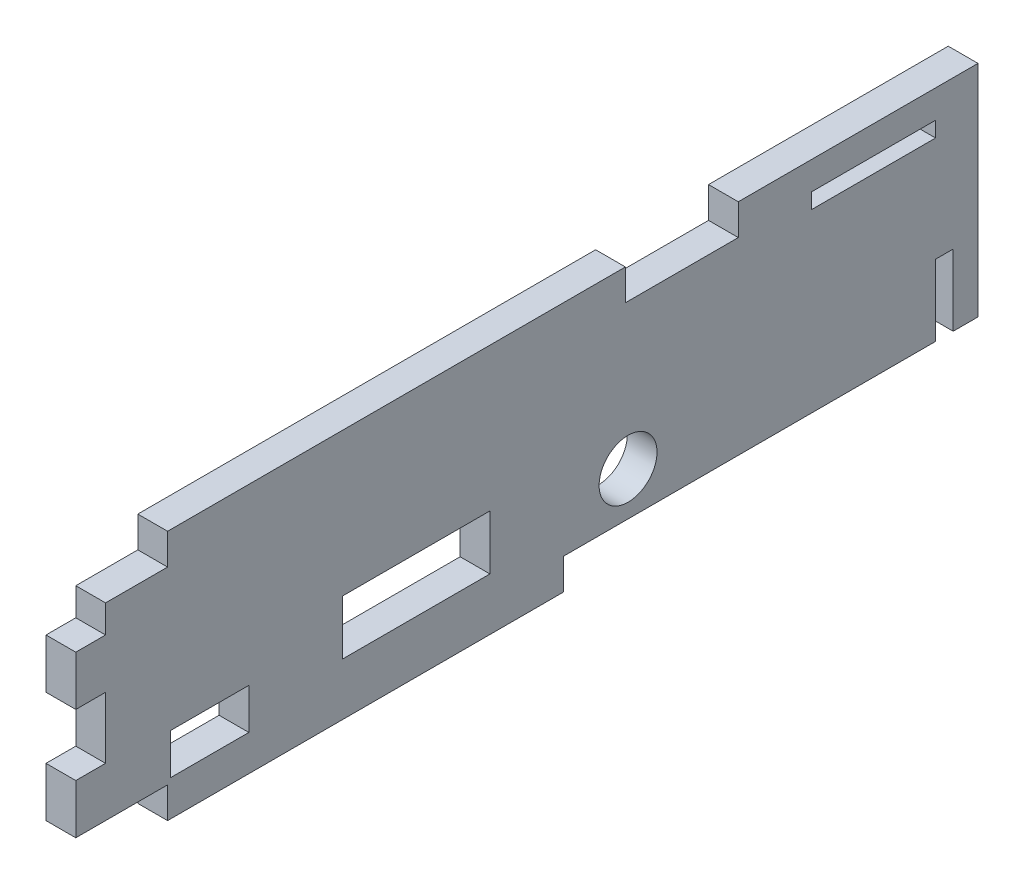
SolidWorks part; units mm, degrees
ref_plane "Front" through (0, 0, 0) normal (0, 0, 1) x (1, 0, 0)
ref_plane "Top" through (0, 0, 0) normal (0, 1, 0) x (1, 0, 0)
ref_plane "Right" through (0, 0, 0) normal (1, 0, 0) x (0, 0, -1)
sketch "Sketch2" plane through (0, 0, 0) normal (1, 0, 0) x (0, 0, -1)
  line L0 (0, 4.7244) -> (84.963, 4.7244) construction
  line L1 (0, 24.0284) -> (84.963, 24.0284)
  line L2 (0, 24.0284) -> (0, 0)
  line L3 (0, 0) -> (84.963, 0)
  line L4 (84.963, 24.0284) -> (84.963, 0)
  line L5 (6.6294, 9.3853) -> (14.6685, 9.3853)
  line L6 (6.6294, 9.3853) -> (6.6294, 5.207)
  line L7 (6.6294, 5.207) -> (14.6685, 5.207)
  line L8 (14.6685, 9.3853) -> (14.6685, 5.207)
  line L9 (24.257, 6.9215) -> (39.3446, 6.9215)
  line L10 (24.257, 6.9215) -> (24.257, 12.5095)
  line L11 (24.257, 12.5095) -> (39.3446, 12.5095)
  line L12 (39.3446, 6.9215) -> (39.3446, 12.5095)
  line L13 (53.486, 12.1412) -> (53.486, 4.7244) construction
  line L14 (6.35, 24.0284) -> (6.35, 27.2034)
  line L15 (6.35, 27.2034) -> (53.213, 27.2034)
  line L16 (84.963, 24.0284) -> (86.7664, 24.0284)
  line L17 (6.35, 4.7244) -> (6.35, 1.5494)
  line L18 (6.35, 1.5494) -> (46.863, 1.5494)
  line L19 (46.863, 1.5494) -> (46.863, 4.7244)
  line L20 (46.863, 4.7244) -> (84.963, 4.7244)
  line L21 (6.35, 4.7244) -> (0, 4.7244)
  line L22 (86.7664, 24.0284) -> (86.7664, 4.7244)
  line L23 (86.7664, 24.0284) -> (89.3064, 24.0284)
  line L24 (89.3064, 24.0284) -> (89.3064, 4.7244)
  line L25 (84.963, 12.0142) -> (86.7664, 12.0142)
  line L26 (86.7664, 4.7244) -> (89.3064, 4.7244)
  line L27 (84.963, 22.7584) -> (72.263, 22.7584)
  line L28 (42.4815, 24.0284) -> (42.4815, 0) construction
  line L29 (-3.048, 4.7244) -> (0, 4.7244)
  line L30 (-3.048, 9.8044) -> (-3.048, 4.7244)
  line L31 (-3.048, 9.8044) -> (0, 9.8044)
  line L32 (-3.048, 16.1036) -> (0, 16.1036)
  line L33 (-3.048, 21.1836) -> (-3.048, 16.1036)
  line L34 (0, 21.1836) -> (-3.048, 21.1836)
  line L35 (53.213, 27.2034) -> (53.213, 24.0284)
  line L36 (72.263, 22.7584) -> (72.263, 24.5618)
  line L37 (72.263, 24.5618) -> (84.963, 24.5618)
  line L38 (84.963, 24.5618) -> (84.963, 24.0284)
  line L39 (89.3064, 24.0284) -> (89.3064, 27.2034)
  line L40 (89.3064, 27.2034) -> (64.77, 27.2034)
  line L41 (64.77, 27.2034) -> (64.77, 24.0284)
  circle A0 centre (53.486, 9.1758) radius 2.9655
  dimension "D11" = 5.9309
  dimension "D13" = 11.176
  dimension "D1" = 84.963
  dimension "D2" = 8.0391
  dimension "D3" = 15.0876
  dimension "D4" = 4.6609
  dimension "D5" = 4.1783
  dimension "D6" = 6.6294
  dimension "D7" = 7.7851
  dimension "D8" = 5.588
  dimension "D9" = 9.5885
  dimension "D10" = 4.7244
  dimension "D12" = 7.4168
  dimension "D14" = 19.304
  dimension "D15" = 6.35
  dimension "D16" = 3.175
  dimension "D17" = 3.175
  dimension "D18" = 38.1
  dimension "D19" = 3.048
  dimension "D20" = 2.8448
  dimension "D21" = 5.08
  dimension "D22" = 5.08
  dimension "D23" = 31.75
  dimension "D24" = 1.8034
  dimension "D25" = 1.27
  dimension "D26" = 12.7
extrude "Boss-Extrude1" add sketch "Sketch2" along normal blind 3.048 contours L21 L17 L18 L19 L20 L4 L1 L2 A0 L12 L9 L10 L11 L5 L8 L7 L6 | L23 L4 | L4 | L15 L14 L1 | L2 L34 L33 L32 | L31 L30 L29 L2 | L22 L26 L24 L23 | L40 L41 L1 L36 L37 L38 L16 L23 L39 region at (0, 13.8682, -41.8848) region at (0, 25.6159, -29.7815) region at (0, 18.6436, 1.524) region at (0, 25.7417, -76.8882) region at (0, 7.2644, 1.524) region at (0, 18.0213, -85.8647) region at (0, 14.3764, -88.0364)
sketch "Sketch3" plane through (0, 0, 0) normal (-1, 0, 0) x (0, 0, 1)
  line L0 (-72.263, 22.7584) -> (-72.263, 24.5618) construction
  line L1 (-84.963, 24.5618) -> (-72.263, 24.5618)
  line L2 (-84.963, 24.5618) -> (-84.963, 24.3332)
  line L3 (-84.963, 24.3332) -> (-72.263, 24.3332)
  line L4 (-72.263, 24.5618) -> (-72.263, 24.3332)
  line L5 (-84.963, 22.7584) -> (-72.263, 22.7584) construction
  dimension "D1" = 1.5748
extrude "made hood slot smaller" add sketch "Sketch3" against normal up to vertex (3.048 mm away) up to point (3.048, 27.2034, -64.77)
sketch "Sketch4" plane through (3.048, 0, 0) normal (1, 0, 0) x (0, 0, -1)
  line B0 (6.6294, 5.207) -> (14.6685, 5.207)
  line B1 (24.257, 6.9215) -> (39.3446, 6.9215)
  line B2 (14.6685, 9.3853) -> (14.6685, 5.207)
  line B3 (6.6294, 9.3853) -> (14.6685, 9.3853)
  line B4 (6.6294, 9.3853) -> (6.6294, 5.207)
  line B5 (24.257, 6.9215) -> (24.257, 12.5095)
  line B6 (24.257, 12.5095) -> (39.3446, 12.5095)
  line B7 (39.3446, 6.9215) -> (39.3446, 12.5095)
  line B8 (46.863, 4.7244) -> (84.963, 4.7244)
  line B9 (0, 16.1036) -> (0, 9.8044)
  circle B10 centre (53.486, 9.1758) radius 2.9655
sketch_block_instance "Block1-1"
sketch_block "Block1"
